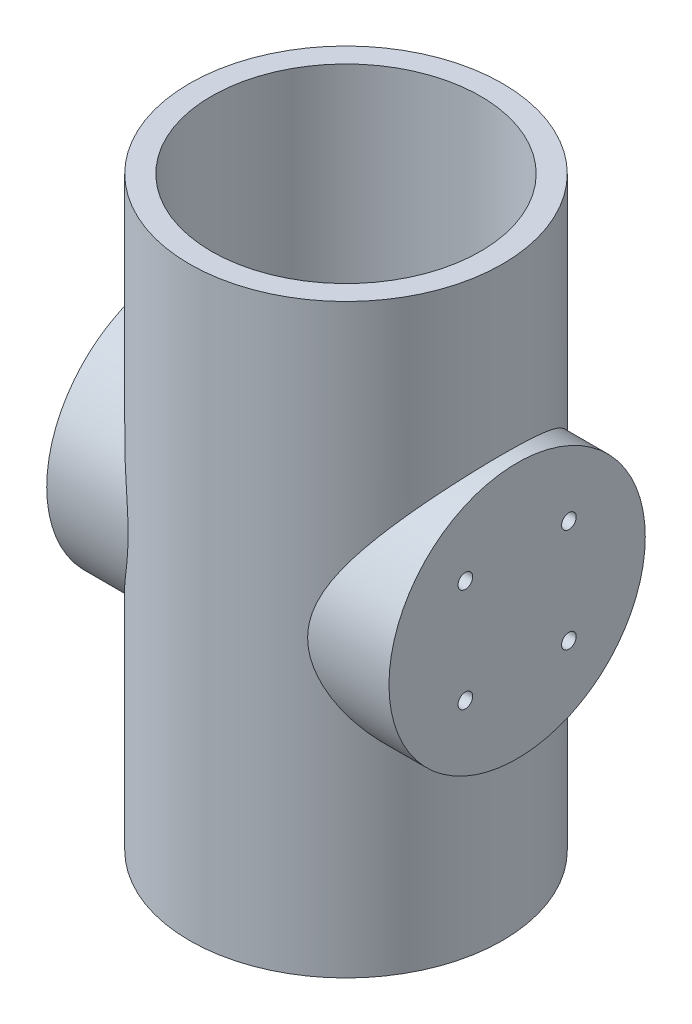
SolidWorks part; units mm, degrees
ref_plane "Front Plane" through (0, 0, 0) normal (0, 0, 1) x (1, 0, 0)
ref_plane "Top Plane" through (0, 0, 0) normal (0, 1, 0) x (1, 0, 0)
ref_plane "Right Plane" through (0, 0, 0) normal (1, 0, 0) x (0, 0, -1)
sketch "Sketch3" plane through (0, 0, 0) normal (0, 1, 0) x (1, 0, 0)
  circle A0 centre (0, 0) radius 15.367 construction
  circle A1 centre (0, 0) radius 18.367
  circle A2 centre (0, 0) radius 21.367
  dimension "D1" = 30.734
  dimension "D2" = 3
  dimension "D3" = 3
extrude "Boss-Extrude1" add sketch "Sketch3" along normal mid plane 80
ref_plane "Plane1" through (21.367, 0, 0) normal (1, 0, 0) x (0, 0, -1)
sketch "Sketch5" plane through (21.367, 0, 0) normal (1, 0, 0) x (0, 0, -1)
  line L0 (-7.0711, 7.0711) -> (0, 0) construction
  circle A0 centre (0, 0) radius 17.5
  circle A1 centre (-7.0711, 7.0711) radius 1
  circle A2 centre (7.0711, 7.0711) radius 1
  circle A3 centre (7.0711, -7.0711) radius 1
  circle A4 centre (-7.0711, -7.0711) radius 1
  point P5 (0, 0)
  point P6 (7.0711, -7.0711)
  point P7 (-7.0711, -7.0711)
  point P14 (0, 0)
  dimension "D3" = 2
  dimension "D4" = 35
  dimension "D2" = 10
  dimension "D5" = 4
  dimension "D1" = 45
extrude "Boss-Extrude2" add sketch "Sketch5" against normal up to surface and the other way blind 2 up to face at (0, 40, 18.367)
mirror "Mirror1" about plane through (0, 0, 0) normal (1, 0, 0) of "Boss-Extrude2"
